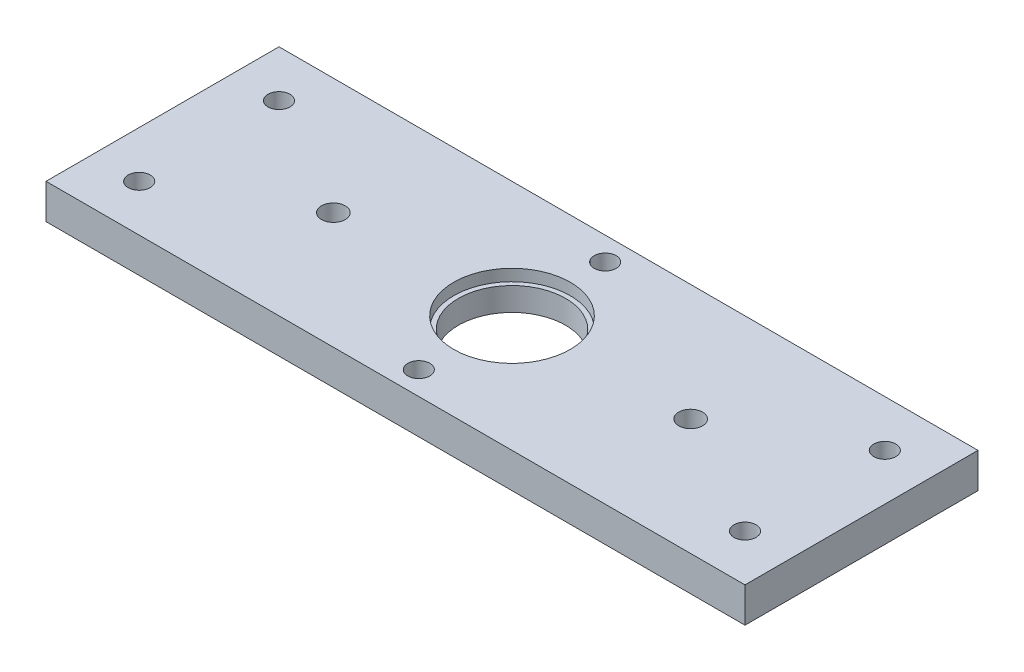
SolidWorks part; units mm, degrees
ref_plane "Front Plane" through (0, 0, 0) normal (0, 0, 1) x (1, 0, 0)
ref_plane "Top Plane" through (0, 0, 0) normal (0, 1, 0) x (1, 0, 0)
ref_plane "Right Plane" through (0, 0, 0) normal (1, 0, 0) x (0, 0, -1)
sketch "Sketch1" plane through (0, 0, 0) normal (0, 1, 0) x (1, 0, 0)
  line L1 (-95.25, -31.75) -> (95.25, -31.75)
  line L2 (-95.25, -31.75) -> (-95.25, 31.75)
  line L3 (-95.25, 31.75) -> (95.25, 31.75)
  line L4 (95.25, -31.75) -> (95.25, 31.75)
  line L5 (-95.25, -31.75) -> (95.25, 31.75) construction
  line L6 (-95.25, 31.75) -> (95.25, -31.75) construction
  point P0 (0, 0)
  dimension "D1" = 190.5
  dimension "D2" = 63.5
extrude "Boss-Extrude1" add sketch "Sketch1" along normal blind 9.525
sketch "Sketch2" plane through (0, 9.525, 0) normal (0, 1, 0) x (1, 0, 0)
  line L0 (-31.75, -31.75) -> (-31.75, 31.75)
  line L1 (-95.25, -31.75) -> (95.25, -31.75) construction
  line L2 (95.25, 31.75) -> (-95.25, 31.75) construction
  line L3 (-95.25, 31.75) -> (-95.25, -31.75) construction
  line L4 (31.75, 31.75) -> (31.75, -31.75)
  line L5 (95.25, -31.75) -> (95.25, 31.75) construction
  dimension "D1" = 63.5
  dimension "D2" = 63.5
sketch "Sketch3" plane through (0, 9.525, 0) normal (0, 1, 0) x (1, 0, 0)
  circle A0 centre (0, 0) radius 14.605
  dimension "D1" = 29.21
extrude "Cut-Extrude1" cut sketch "Sketch3" against normal through all
sketch "Sketch6" plane through (0, 0, 31.75) normal (0, 0, 1) x (1, 0, 0)
  line L0 (-31.75, 9.525) -> (-31.75, 0)
  line L1 (-95.25, 0) -> (95.25, 0) construction
sketch "Sketch7" plane through (0, 0, 0) normal (0, -1, 0) x (1, 0, 0)
  line L0 (-31.75, 31.75) -> (-31.75, -31.75)
  line L1 (95.25, -31.75) -> (-95.25, -31.75) construction
sketch "Sketch8" plane through (0, 0, 31.75) normal (0, 0, 1) x (1, 0, 0)
  line L0 (31.75, 9.525) -> (31.75, 0)
  line L1 (-95.25, 0) -> (95.25, 0) construction
sketch "Sketch9" plane through (0, 0, 0) normal (0, -1, 0) x (1, 0, 0)
  line L0 (31.75, 31.75) -> (31.75, -31.75)
  line L1 (95.25, -31.75) -> (-95.25, -31.75) construction
hole_wizard "Ø6.0 (6) Diameter Hole1" positions "Sketch22" profile "Sketch23" hole size "Ø6.0" standard "ANSI Metric" end condition through all
sketch "Sketch22" plane through (0, 0, 0) normal (0, -1, 0) x (-1, 0, 0)
  point P0 (0, -25.4)
  point P2 (0, 25.4)
  dimension "D1" = 25.4
  dimension "D2" = 25.4
sketch "Sketch23" plane through (0, 0, 25.4) normal (1, 0, 0) x (0, 0, -1)
  line L0 (0, 0) -> (0, 9.525)
  line L1 (0, 9.525) -> (3, 9.525)
  line L2 (3, 9.525) -> (3, 0)
  line L5 (3, 0) -> (0, 0)
  line L11 (0, -6.35) -> (0, 107.95) construction
  dimension "Thru Hole Dia." = 6
  dimension "Thru Hole Depth" = 9.525
hole_wizard "Ø6.5 (6.5) Diameter Hole3" positions "Sketch24" profile "Sketch25" hole size "Ø6.5" standard "ANSI Metric" end condition through all
sketch "Sketch24" plane through (0, 0, 0) normal (0, -1, 0) x (-1, 0, 0)
  line L0 (31.75, -31.75) -> (31.75, 31.75) construction
  line L1 (-31.75, 31.75) -> (-31.75, -31.75) construction
  point P0 (48.6833, 0)
  point P2 (-48.6833, 0)
  dimension "D1" = 16.9333
  dimension "D2" = 16.9333
sketch "Sketch25" plane through (-48.6833, 0, 0) normal (1, 0, 0) x (0, 0, -1)
  line L0 (0, 0) -> (0, 9.525)
  line L1 (0, 9.525) -> (3.25, 9.525)
  line L2 (3.25, 9.525) -> (3.25, 0)
  line L5 (3.25, 0) -> (0, 0)
  line L11 (0, -6.35) -> (0, 107.95) construction
  dimension "Thru Hole Dia." = 6.5
  dimension "Thru Hole Depth" = 9.525
sketch "Sketch29" plane through (0, 9.525, 0) normal (0, 1, 0) x (1, 0, 0)
  circle A0 centre (0, 0) radius 15.875
extrude "Cut-Extrude5" cut sketch "Sketch29" against normal blind 3.175
hole_wizard "Ø6.0 (6) Diameter Hole3" positions "Sketch32" profile "Sketch31" hole size "Ø6.0" standard "ANSI Metric" end condition through all
sketch "Sketch32" plane through (0, 9.525, 0) normal (0, 1, 0) x (1, 0, 0)
  line L0 (95.25, 31.75) -> (-95.25, 31.75) construction
  line L1 (-95.25, 31.75) -> (-95.25, -31.75) construction
  line L2 (-95.25, -31.75) -> (95.25, -31.75) construction
  line L3 (95.25, -31.75) -> (95.25, 31.75) construction
  point P0 (-82.55, 19.05)
  point P2 (-82.55, -19.05)
  point P4 (82.55, -19.05)
  point P6 (82.55, 19.05)
  point P21 (89.857, 35.6769)
  dimension "D1" = 12.7
  dimension "D2" = 12.7
  dimension "D3" = 12.7
  dimension "D4" = 12.7
  dimension "D5" = 12.7
  dimension "D6" = 12.7
  dimension "D7" = 12.7
  dimension "D8" = 12.7
sketch "Sketch31" plane through (-82.55, 9.525, -19.05) normal (1, 0, 0) x (0, 0, 1)
  line L0 (0, 0) -> (0, 9.525)
  line L1 (0, 9.525) -> (3, 9.525)
  line L2 (3, 9.525) -> (3, 0)
  line L5 (3, 0) -> (0, 0)
  line L11 (0, -6.35) -> (0, 107.95) construction
  dimension "Thru Hole Dia." = 6
  dimension "Thru Hole Depth" = 9.525
